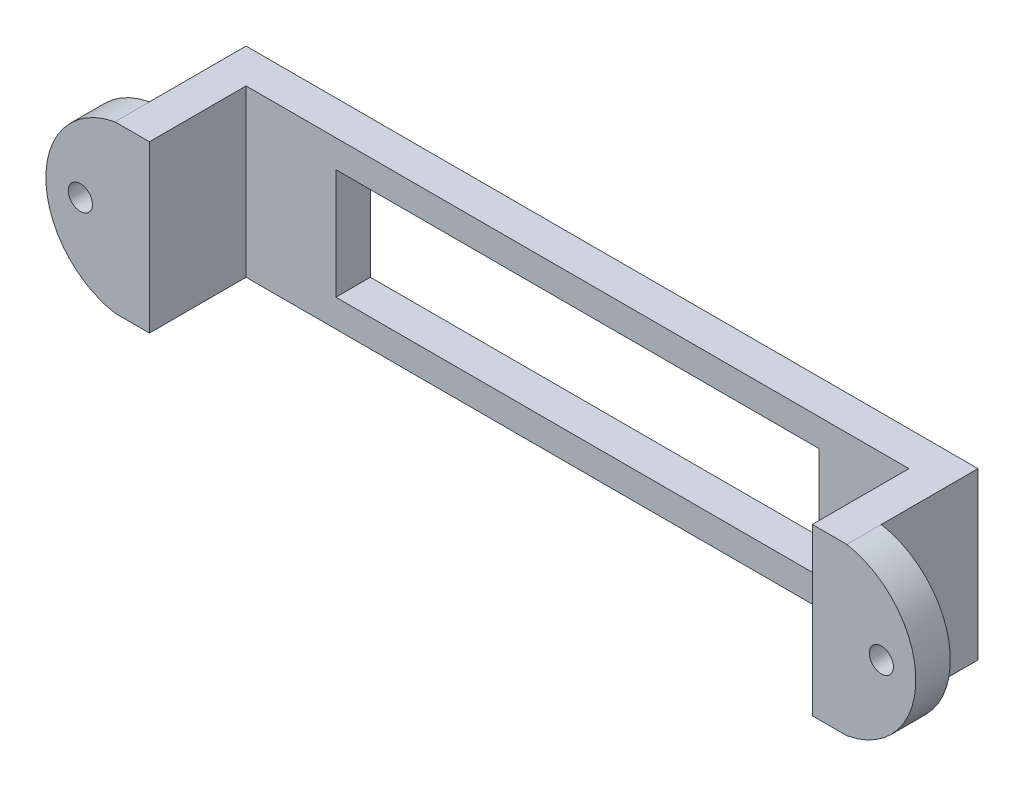
SolidWorks part; units mm, degrees
ref_plane "Plan de face" through (0, 0, 0) normal (0, 0, 1) x (1, 0, 0)
ref_plane "Plan de dessus" through (0, 0, 0) normal (0, 1, 0) x (1, 0, 0)
ref_plane "Plan de droite" through (0, 0, 0) normal (1, 0, 0) x (0, 0, -1)
sketch "Esquisse1" plane through (0, 0, 0) normal (0, 0, 1) x (1, 0, 0)
  line L0 (0, -37.6975) -> (0, 37.6975) construction
  line L1 (-48, 17) -> (48, 17)
  line L2 (-48, 17) -> (-48, -17)
  line L3 (-48, -17) -> (48, -17)
  line L4 (48, 17) -> (48, -17)
  line L5 (-10, 0) -> (10, 0) construction
  line L6 (-35, 8) -> (35, 8)
  line L7 (-53, 12) -> (53, 12)
  line L8 (-53, 12) -> (-53, -12)
  line L9 (-53, -12) -> (53, -12)
  line L10 (53, 12) -> (53, -12)
  line L15 (-35, 8) -> (-35, -8)
  line L16 (-35, -8) -> (35, -8)
  line L17 (35, 8) -> (35, -8)
  point P6 (0, 0)
  point P13 (-48, 0)
  point P14 (48, 0)
  dimension "D1" = 5
  dimension "D2" = 34
  dimension "D3" = 96
  dimension "D4" = 70
  dimension "D5" = 16
  dimension "D6" = 5
extrude "Boss.-Extru.1" add sketch "Esquisse1" along normal blind 5 contours L8 L9 L2 L7 | L2 L9 L4 L7 L6 L17 L16 L15 | L10 L7 L4 L9 region at (0, 11.0105, 0) region at (-50.5, 0, 0) region at (50.5, 0, 0)
sketch "Esquisse2" plane through (0, 0, 5) normal (0, 0, 1) x (1, 0, 0)
  line L0 (-53, -12) -> (53, -12) construction
  line L1 (-53, 12) -> (-48, 12)
  line L2 (-53, 12) -> (-53, -12)
  line L3 (-53, -12) -> (-48, -12)
  line L4 (-48, 12) -> (-48, -12)
  line L5 (0, 12) -> (0, -12) construction
  line L6 (53, 12) -> (48, 12)
  line L7 (53, 12) -> (53, -12)
  line L8 (53, -12) -> (48, -12)
  line L9 (48, 12) -> (48, -12)
  line L10 (-53, 12) -> (53, 12) construction
  dimension "D1" = 5
extrude "Boss.-Extru.2" add sketch "Esquisse2" along normal blind 9
sketch "Esquisse3" plane through (0, 0, 14) normal (0, 0, 1) x (1, 0, 0)
  line L1 (-48, -12) -> (48, -12) construction
  line L2 (-48, 12) -> (-53, 12)
  line L3 (-48, 12) -> (-48, -12)
  line L4 (-48, -12) -> (-53, -12)
  line L6 (0, 12) -> (0, -12) construction
  line L7 (-48, 12) -> (48, 12) construction
  line L11 (-53, 12) -> (-53, -12) construction
  line L12 (48, -12) -> (53, -12)
  line L13 (48, 12) -> (48, -12)
  line L14 (48, 12) -> (53, 12)
  arc A0 (-53, 12) -> (-53, -12) centre (-50.8, 0) ccw
  arc A1 (53, 12) -> (53, -12) centre (50.8, 0) cw
  point P7 (-63, 0)
  point P21 (63, 0)
  dimension "D1" = 10
extrude "Boss.-Extru.3" add sketch "Esquisse3" along normal blind 5
sketch "Esquisse4" plane through (0, 0, 19) normal (0, 0, 1) x (1, 0, 0)
  line L0 (-63, 0) -> (0, 0) construction
  line L1 (0, 12) -> (0, -12) construction
  line L2 (-48, 12) -> (48, 12) construction
  line L3 (-48, -12) -> (48, -12) construction
  circle A0 centre (-58, 0) radius 1.75
  arc A1 (-53, 12) -> (-53, -12) centre (-50.8, 0) ccw construction
  circle A2 centre (58, 0) radius 1.75
  point P2 (-63, 0)
  point P17 (63, 0)
  dimension "D1" = 3.5
  dimension "D2" = 5
extrude "Enlèv. mat.-Extru.2" cut sketch "Esquisse4" against normal through all
ref_plane "Plan1" through (-53, -12, 0) normal (0, -1, 0) x (-1, 0, 0)
